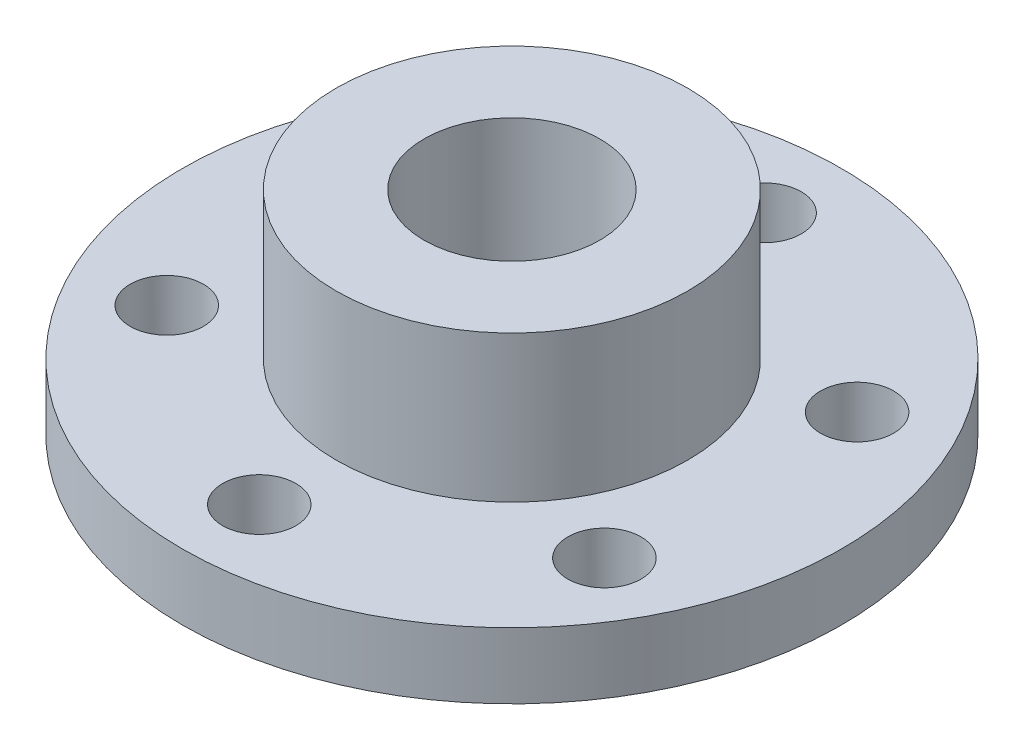
SolidWorks part; units mm, degrees
ref_plane "Front Plane" through (0, 0, 0) normal (0, 0, 1) x (1, 0, 0)
ref_plane "Top Plane" through (0, 0, 0) normal (0, 1, 0) x (1, 0, 0)
ref_plane "Right Plane" through (0, 0, 0) normal (1, 0, 0) x (0, 0, -1)
sketch "Sketch1" plane through (0, 0, 0) normal (0, 1, 0) x (1, 0, 0)
  circle A0 centre (0, 0) radius 22.5
  dimension "D1" = 45
extrude "Boss-Extrude1" add sketch "Sketch1" along normal blind 4.5
sketch "Sketch2" plane through (0, 4.5, 0) normal (0, 1, 0) x (1, 0, 0)
  circle A0 centre (0, 0) radius 12
  dimension "D1" = 24
extrude "Boss-Extrude2" add sketch "Sketch2" along normal blind 10
sketch "Sketch3" plane through (0, 14.5, 0) normal (0, 1, 0) x (1, 0, 0)
  circle A0 centre (0, 0) radius 6
  dimension "D1" = 12
extrude "Cut-Extrude1" cut sketch "Sketch3" against normal blind 21
sketch "Sketch4" plane through (0, 0, 0) normal (0, -1, 0) x (1, 0, 0)
  circle A0 centre (0, 17.25) radius 2.5
  circle A1 centre (14.9389, 8.625) radius 2.5
  circle A2 centre (14.9389, -8.625) radius 2.5
  circle A3 centre (0, -17.25) radius 2.5
  circle A4 centre (-14.9389, -8.625) radius 2.5
  circle A5 centre (-14.9389, 8.625) radius 2.5
  point P15 (0, 0)
  dimension "D1" = 5
  dimension "D2" = 17.25
  dimension "D3" = 6
extrude "Cut-Extrude2" cut sketch "Sketch4" against normal blind 10
